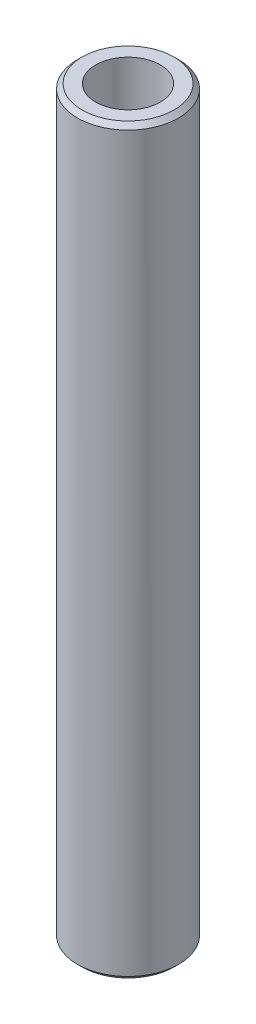
SolidWorks part; units mm, degrees
ref_plane "Front Plane" through (0, 0, 0) normal (0, 0, 1) x (1, 0, 0)
ref_plane "Top Plane" through (0, 0, 0) normal (0, 1, 0) x (1, 0, 0)
ref_plane "Right Plane" through (0, 0, 0) normal (1, 0, 0) x (0, 0, -1)
sketch "Sketch1" plane through (0, 0, 0) normal (0, 1, 0) x (1, 0, 0)
  circle A0 centre (0, 0) radius 20
  dimension "SHAFT_OD" = 40
extrude "Boss-Extrude1" add sketch "Sketch1" along normal blind 293.4187
sketch "Sketch2" plane through (0, 0, 0) normal (0, 1, 0) x (1, 0, 0)
  circle A0 centre (0, 0) radius 12.7663
  dimension "BORE_D" = 25.5326
extrude "Cut-Extrude1" cut sketch "Sketch2" along normal through all
chamfer "Chamfer1" distance 1.8269 angle 45 2 edges at (0, 293.4187, 20) (0, 0, 20)
